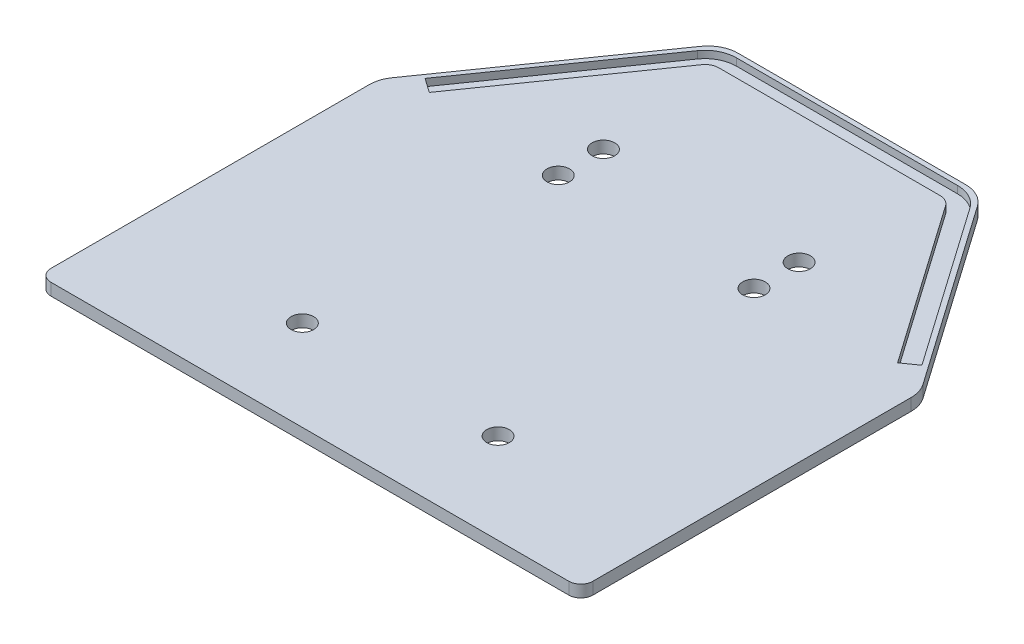
SolidWorks part; units mm, degrees
note: The reader was unsure of these and kept them because the rebuilt part matched: shared geometry of "Sketch5<5>".
ref_plane "Front Plane" through (0, 0, 0) normal (0, 0, 1) x (1, 0, 0)
ref_plane "Top Plane" through (0, 0, 0) normal (0, 1, 0) x (1, 0, 0)
ref_plane "Right Plane" through (0, 0, 0) normal (1, 0, 0) x (0, 0, -1)
sketch "TruckMountingHoles" plane through (0, 0, 0) normal (0, 1, 0) x (1, 0, 0)
  line L0 (-20.6375, 22.225) -> (20.6375, 22.225) construction
  line L1 (-20.6375, -31.75) -> (20.6375, -31.75)
  line L2 (-20.6375, -31.75) -> (-20.6375, 31.75)
  line L3 (-20.6375, 31.75) -> (20.6375, 31.75)
  line L4 (20.6375, -31.75) -> (20.6375, 31.75)
  line L5 (-20.6375, -31.75) -> (20.6375, 31.75) construction
  line L6 (-20.6375, 31.75) -> (20.6375, -31.75) construction
  circle A0 centre (-20.6375, 22.225) radius 2.3813
  circle A1 centre (-20.6375, 31.75) radius 2.3813
  circle A2 centre (20.6375, 31.75) radius 2.3813
  circle A3 centre (20.6375, 22.225) radius 2.3813
  circle A4 centre (20.6375, -31.75) radius 2.3813
  circle A5 centre (-20.6375, -31.75) radius 2.3813
  point P0 (0, 0)
  dimension "D3" = 4.7625
  dimension "D1" = 41.275
  dimension "D2" = 63.5
  dimension "D4" = 53.975
sketch "Sketch2" plane through (0, 0, 0) normal (0, 1, 0) x (1, 0, 0)
  line L1 (-57.15, -50.8) -> (57.15, -50.8)
  line L2 (-57.15, -50.8) -> (-57.15, 50.8)
  line L3 (-57.15, 50.8) -> (57.15, 50.8)
  line L4 (57.15, -50.8) -> (57.15, 50.8)
  line L5 (-57.15, -50.8) -> (57.15, 50.8) construction
  line L6 (-57.15, 50.8) -> (57.15, -50.8) construction
  point P0 (0, 0)
  dimension "D1" = 114.3
  dimension "D2" = 101.6
extrude "Boss-Extrude1" add sketch "Sketch2" along normal blind 2.54
sketch "Sketch3" plane through (0, 2.54, 0) normal (0, 1, 0) x (1, 0, 0)
  line L4 (57.15, 50.8) -> (-57.15, 50.8) construction
  line L5 (-30.1625, -50.8) -> (-11.1125, -50.8)
  line L6 (-30.1625, -50.8) -> (-30.1625, 50.8)
  line L7 (-30.1625, 50.8) -> (-11.1125, 50.8)
  line L13 (-11.1125, -50.8) -> (-11.1125, 50.8)
  line L14 (-30.1625, -50.8) -> (-11.1125, 50.8) construction
  line L15 (-30.1625, 50.8) -> (-11.1125, -50.8) construction
  line L17 (-20.6375, -31.75) -> (-20.6375, 31.75) construction
  line L18 (0, 50.8) -> (0, -50.8) construction
  line L19 (-57.15, -50.8) -> (57.15, -50.8) construction
  line L20 (30.1625, 50.8) -> (11.1125, -50.8) construction
  line L21 (30.1625, -50.8) -> (11.1125, 50.8) construction
  line L22 (11.1125, -50.8) -> (11.1125, 50.8)
  line L23 (30.1625, 50.8) -> (11.1125, 50.8)
  line L24 (30.1625, -50.8) -> (30.1625, 50.8)
  line L25 (30.1625, -50.8) -> (11.1125, -50.8)
  line L26 (-57.15, -50.8) -> (57.15, -50.8)
  line L27 (-30.1625, -12.7) -> (30.1625, -12.7)
  line L28 (-30.1625, -12.7) -> (-30.1625, 12.7)
  line L29 (-30.1625, 12.7) -> (30.1625, 12.7)
  line L30 (30.1625, -12.7) -> (30.1625, 12.7)
  line L31 (-30.1625, -12.7) -> (30.1625, 12.7) construction
  line L32 (-30.1625, 12.7) -> (30.1625, -12.7) construction
  line L33 (-30.1625, 41.7056) -> (-23.7946, 50.8)
  line L35 (-36.2596, 37.4265) -> (-44.9423, 25.0262)
  line L36 (30.1625, 41.7056) -> (23.7946, 50.8)
  point P0 (-20.6375, 0)
  point P17 (20.6375, 0)
  point P18 (0, 0)
  dimension "D1" = 19.05
  dimension "D2" = 25.4
  dimension "D3" = 2.54
extrude "Boss-Extrude2" add sketch "Sketch3" along normal blind 2.54
extrude "Cut-Extrude1" cut sketch "TruckMountingHoles" along normal through all contours A1 | A0 | A4 | A5 | A3 | A2
fillet "Fillet1" radius 2.54 4 edges at (57.15, 1.27, -50.8) (57.15, 1.27, 50.8) (-57.15, 1.27, -50.8) (-57.15, 1.27, 50.8)
sketch "Sketch5" plane through (0, 2.54, 0) normal (0, 1, 0) x (1, 0, 0)
  line L1 (57.15, -48.26) -> (57.15, 48.26) construction
  line L2 (0, 50.8) -> (0, 0) construction
  line L3 (27.305, 63.5) -> (-27.305, 63.5)
  line L4 (23.7946, 50.8) -> (-25.5007, 50.8)
  line L5 (57.15, 20.8769) -> (27.305, 63.5)
  line L6 (-57.15, 20.8769) -> (-27.305, 63.5)
  line L17 (57.15, -48.26) -> (57.15, 48.26)
  line L19 (30.1625, 41.7056) -> (30.1625, 12.7)
  line L20 (30.1625, 12.7) -> (11.1125, 12.7)
  line L21 (11.1125, 12.7) -> (11.1125, 50.8)
  line L22 (11.1125, 50.8) -> (-11.1125, 50.8)
  line L23 (-11.1125, 50.8) -> (-11.1125, 12.7)
  line L24 (-11.1125, 12.7) -> (-30.1625, 12.7)
  line L25 (-30.1625, 12.7) -> (-30.1625, 41.7056)
  line L26 (-23.7946, 50.8) -> (-54.61, 50.8)
  line L27 (-57.15, 48.26) -> (-57.15, -48.26)
  line L28 (-54.61, -50.8) -> (-30.1625, -50.8)
  line L29 (-30.1625, -50.8) -> (-30.1625, -12.7)
  line L30 (-30.1625, -12.7) -> (-11.1125, -12.7)
  line L31 (57.15, -48.26) -> (57.15, 48.26)
  line L51 (30.1625, 41.7056) -> (30.1625, 12.7)
  line L52 (30.1625, 12.7) -> (11.1125, 12.7)
  line L53 (11.1125, 12.7) -> (11.1125, 50.8)
  line L54 (11.1125, 50.8) -> (-11.1125, 50.8)
  line L55 (-11.1125, 50.8) -> (-11.1125, 12.7)
  line L56 (-11.1125, 12.7) -> (-30.1625, 12.7)
  line L57 (-30.1625, 12.7) -> (-30.1625, 41.7056)
  line L58 (-23.7946, 50.8) -> (-54.61, 50.8)
  line L59 (-57.15, 48.26) -> (-57.15, -48.26)
  line L60 (-54.61, -50.8) -> (-30.1625, -50.8)
  line L61 (-30.1625, -50.8) -> (-30.1625, -12.7)
  line L62 (-30.1625, -12.7) -> (-11.1125, -12.7)
  line L71 (54.61, 50.8) -> (23.7946, 50.8)
  line L72 (-30.1625, 41.7056) -> (-23.7946, 50.8)
  line L73 (-30.1625, 41.7056) -> (-23.7946, 50.8)
  line L82 (54.61, 50.8) -> (23.7946, 50.8)
  line L84 (30.1625, -12.7) -> (30.1625, -50.8)
  line L86 (11.1125, -12.7) -> (30.1625, -12.7)
  line L87 (11.1125, -12.7) -> (30.1625, -12.7)
  line L88 (30.1625, -12.7) -> (30.1625, -50.8)
  line L89 (30.1625, -50.8) -> (54.61, -50.8)
  line L90 (30.1625, -50.8) -> (54.61, -50.8)
  line L91 (23.7946, 50.8) -> (30.1625, 41.7056)
  line L92 (23.7946, 50.8) -> (30.1625, 41.7056)
  line L93 (-11.1125, -12.7) -> (-11.1125, -50.8)
  line L94 (-11.1125, -12.7) -> (-11.1125, -50.8)
  line L95 (-11.1125, -50.8) -> (11.1125, -50.8)
  line L96 (-11.1125, -50.8) -> (11.1125, -50.8)
  line L97 (11.1125, -50.8) -> (11.1125, -12.7)
  line L98 (11.1125, -50.8) -> (11.1125, -12.7)
  arc A7 (57.15, 48.26) -> (54.61, 50.8) centre (54.61, 48.26) ccw
  arc A8 (-54.61, 50.8) -> (-57.15, 48.26) centre (-54.61, 48.26) ccw
  arc A13 (-57.15, -48.26) -> (-54.61, -50.8) centre (-54.61, -48.26) ccw
  arc A14 (57.15, 48.26) -> (54.61, 50.8) centre (54.61, 48.26) ccw
  arc A16 (-54.61, 50.8) -> (-57.15, 48.26) centre (-54.61, 48.26) ccw
  arc A17 (-57.15, -48.26) -> (-54.61, -50.8) centre (-54.61, -48.26) ccw
  arc A18 (54.61, -50.8) -> (57.15, -48.26) centre (54.61, -48.26) ccw
  arc A19 (54.61, -50.8) -> (57.15, -48.26) centre (54.61, -48.26) ccw
  dimension "D1" = 0
  dimension "D2" = 12.7
  dimension "D3" = 54.61
extrude "Cut-Extrude3" cut sketch "Sketch5" against normal through all and the other way through all
extrude "Boss-Extrude3" add sketch "Sketch5<5>" against normal up to surface (2.54 mm away) up to face at (20.6375, 0, -29.3687)
sketch "Sketch5<5>" plane through (0, 2.54, 0) normal (0, 1, 0) x (1, 0, 0) same geometry as "Sketch5"
sketch "Sketch6" plane through (0, 2.54, 0) normal (0, 1, 0) x (1, 0, 0)
  line L8 (25.9391, 57.7011) -> (49.4458, 24.13)
  line L9 (-23.3383, 59.055) -> (23.3383, 59.055)
  line L10 (-49.4458, 24.13) -> (-25.9391, 57.7011)
  line L11 (-52.0466, 25.9511) -> (-49.4458, 24.13)
  line L12 (-28.5399, 59.5222) -> (-52.0466, 25.9511)
  line L13 (23.3383, 62.23) -> (-23.3383, 62.23)
  line L14 (52.0466, 25.9511) -> (28.5399, 59.5222)
  line L15 (49.4458, 24.13) -> (52.0466, 25.9511)
  line L16 (25.9391, 57.7011) -> (49.4458, 24.13)
  line L17 (-23.3383, 59.055) -> (23.3383, 59.055)
  line L18 (-49.4458, 24.13) -> (-25.9391, 57.7011)
  line L19 (-52.0466, 25.9511) -> (-49.4458, 24.13)
  line L20 (-28.5399, 59.5222) -> (-52.0466, 25.9511)
  line L21 (23.3383, 62.23) -> (-23.3383, 62.23)
  line L22 (52.0466, 25.9511) -> (28.5399, 59.5222)
  line L23 (49.4458, 24.13) -> (52.0466, 25.9511)
  line L24 (49.3835, 23.7762) -> (52.4004, 25.8887)
  line L25 (25.731, 57.5554) -> (49.3835, 23.7762)
  line L26 (-23.3383, 58.801) -> (23.3383, 58.801)
  line L27 (-49.3835, 23.7762) -> (-25.731, 57.5554)
  line L28 (-52.4004, 25.8887) -> (-49.3835, 23.7762)
  line L29 (-28.748, 59.6679) -> (-52.4004, 25.8887)
  line L30 (23.3383, 62.484) -> (-23.3383, 62.484)
  line L31 (52.4004, 25.8887) -> (28.748, 59.6679)
  line L32 (49.3835, 23.7762) -> (52.4004, 25.8887)
  line L33 (25.731, 57.5554) -> (49.3835, 23.7762)
  line L34 (-23.3383, 58.801) -> (23.3383, 58.801)
  line L35 (-49.3835, 23.7762) -> (-25.731, 57.5554)
  line L36 (-52.4004, 25.8887) -> (-49.3835, 23.7762)
  line L37 (-28.748, 59.6679) -> (-52.4004, 25.8887)
  line L38 (23.3383, 62.484) -> (-23.3383, 62.484)
  line L39 (52.4004, 25.8887) -> (28.748, 59.6679)
  arc A4 (25.9391, 57.7011) -> (23.3383, 59.055) centre (23.3383, 55.88) ccw
  arc A5 (-23.3383, 59.055) -> (-25.9391, 57.7011) centre (-23.3383, 55.88) ccw
  arc A6 (-23.3383, 62.23) -> (-28.5399, 59.5222) centre (-23.3383, 55.88) ccw
  arc A7 (28.5399, 59.5222) -> (23.3383, 62.23) centre (23.3383, 55.88) ccw
  arc A8 (25.9391, 57.7011) -> (23.3383, 59.055) centre (23.3383, 55.88) ccw
  arc A9 (-23.3383, 59.055) -> (-25.9391, 57.7011) centre (-23.3383, 55.88) ccw
  arc A10 (-23.3383, 62.23) -> (-28.5399, 59.5222) centre (-23.3383, 55.88) ccw
  arc A11 (28.5399, 59.5222) -> (23.3383, 62.23) centre (23.3383, 55.88) ccw
  arc A12 (25.731, 57.5554) -> (23.3383, 58.801) centre (23.3383, 55.88) ccw
  arc A13 (-23.3383, 58.801) -> (-25.731, 57.5554) centre (-23.3383, 55.88) ccw
  arc A14 (-23.3383, 62.484) -> (-28.748, 59.6679) centre (-23.3383, 55.88) ccw
  arc A15 (28.748, 59.6679) -> (23.3383, 62.484) centre (23.3383, 55.88) ccw
  arc A16 (25.731, 57.5554) -> (23.3383, 58.801) centre (23.3383, 55.88) ccw
  arc A17 (-23.3383, 58.801) -> (-25.731, 57.5554) centre (-23.3383, 55.88) ccw
  arc A18 (-23.3383, 62.484) -> (-28.748, 59.6679) centre (-23.3383, 55.88) ccw
  arc A19 (28.748, 59.6679) -> (23.3383, 62.484) centre (23.3383, 55.88) ccw
  dimension "D1" = 0
  dimension "D2" = 0
extrude "Cut-Extrude4" cut sketch "Sketch6" against normal offset from surface (1.526 mm away) 0.254 contours A19 L38 A18 L37 L36 L35 A17 L34 A16 L33 L32 L39
fillet "Fillet2" radius 6.35 4 edges at (-57.15, 1.27, -20.8769) (-27.305, 1.27, -63.5) (27.305, 1.27, -63.5) (57.15, 1.27, -20.8769)
sketch "Sketch7" plane through (0, 0, 0) normal (0, -1, 0) x (1, 0, 0)
  line L1 (57.15, 48.26) -> (57.15, -18.8748) construction
  line L2 (56.0016, -22.517) -> (29.201, -60.7922) construction
  point P0 (57.15, -20.8769)
sketch "Sketch8" plane through (0, 2.54, 0) normal (0, 1, 0) x (1, 0, 0)
  line L0 (-11.1125, -48.26) -> (11.1125, -48.26)
  line L14 (-29.201, 60.7922) -> (-56.0016, 22.517)
  line L15 (-57.15, 18.8748) -> (-57.15, -48.26)
  line L16 (-54.61, -50.8) -> (-30.1625, -50.8)
  line L17 (-30.1625, -50.8) -> (-30.1625, -12.7)
  line L18 (-30.1625, -12.7) -> (-11.1125, -12.7)
  line L19 (-11.1125, -12.7) -> (-11.1125, -50.8)
  line L20 (-11.1125, -50.8) -> (11.1125, -50.8)
  line L21 (11.1125, -50.8) -> (11.1125, -12.7)
  line L22 (11.1125, -12.7) -> (30.1625, -12.7)
  line L23 (30.1625, -12.7) -> (30.1625, -50.8)
  line L24 (30.1625, -50.8) -> (54.61, -50.8)
  line L25 (57.15, -48.26) -> (57.15, 18.8748)
  line L26 (56.0016, 22.517) -> (29.201, 60.7922)
  line L27 (23.9994, 63.5) -> (-23.9994, 63.5)
  line L28 (-29.201, 60.7922) -> (-56.0016, 22.517)
  line L29 (-57.15, 18.8748) -> (-57.15, -48.26)
  line L30 (-54.61, -50.8) -> (-30.1625, -50.8)
  line L31 (-30.1625, -50.8) -> (-30.1625, -12.7)
  line L32 (-30.1625, -12.7) -> (-11.1125, -12.7)
  line L33 (-11.1125, -12.7) -> (-11.1125, -50.8)
  line L34 (-11.1125, -50.8) -> (11.1125, -50.8)
  line L35 (11.1125, -50.8) -> (11.1125, -12.7)
  line L36 (11.1125, -12.7) -> (30.1625, -12.7)
  line L37 (30.1625, -12.7) -> (30.1625, -50.8)
  line L38 (30.1625, -50.8) -> (54.61, -50.8)
  line L39 (57.15, -48.26) -> (57.15, 18.8748)
  line L40 (56.0016, 22.517) -> (29.201, 60.7922)
  line L41 (23.9994, 63.5) -> (-23.9994, 63.5)
  arc A6 (-56.0016, 22.517) -> (-57.15, 18.8748) centre (-50.8, 18.8748) ccw
  arc A7 (-57.15, -48.26) -> (-54.61, -50.8) centre (-54.61, -48.26) ccw
  arc A8 (54.61, -50.8) -> (57.15, -48.26) centre (54.61, -48.26) ccw
  arc A9 (57.15, 18.8748) -> (56.0016, 22.517) centre (50.8, 18.8748) ccw
  arc A10 (29.201, 60.7922) -> (23.9994, 63.5) centre (23.9994, 57.15) ccw
  arc A11 (-23.9994, 63.5) -> (-29.201, 60.7922) centre (-23.9994, 57.15) ccw
  arc A12 (-56.0016, 22.517) -> (-57.15, 18.8748) centre (-50.8, 18.8748) ccw
  arc A13 (-57.15, -48.26) -> (-54.61, -50.8) centre (-54.61, -48.26) ccw
  arc A14 (54.61, -50.8) -> (57.15, -48.26) centre (54.61, -48.26) ccw
  arc A15 (57.15, 18.8748) -> (56.0016, 22.517) centre (50.8, 18.8748) ccw
  arc A16 (29.201, 60.7922) -> (23.9994, 63.5) centre (23.9994, 57.15) ccw
  arc A17 (-23.9994, 63.5) -> (-29.201, 60.7922) centre (-23.9994, 57.15) ccw
  line M51 (-11.1125, -12.7) -> (-11.1125, -50.8)
  line M52 (-11.1125, -50.8) -> (11.1125, -50.8)
  line M53 (11.1125, -50.8) -> (11.1125, -12.7)
  dimension "D2" = 2.54
  dimension "D1" = 0
extrude "Boss-Extrude4" add sketch "Sketch8" along normal up to surface (2.54 mm away) contours L0 M51 M52 M53 up to face at (-20.6375, 5.08, 34.1313)
sketch "Sketch9" plane through (0, 0, 50.8) normal (0, 0, 1) x (1, 0, 0)
  line L0 (11.1125, 9.398) -> (5.08, 9.398) construction
  line L1 (11.1125, 9.398) -> (5.08, 9.398)
  line L4 (-6.35, 8.128) -> (-6.35, 5.18)
  line L5 (-5.08, 3.91) -> (5.08, 3.91)
  line L6 (6.35, 5.18) -> (6.35, 8.128)
  line L7 (5.08, 9.398) -> (-5.08, 9.398)
  line L8 (-6.35, 8.128) -> (-6.35, 5.18)
  line L9 (-5.08, 3.91) -> (5.08, 3.91)
  line L10 (6.35, 5.18) -> (6.35, 8.128)
  line L11 (5.08, 9.398) -> (-5.08, 9.398)
  arc A4 (-6.35, 5.18) -> (-5.08, 3.91) centre (-5.08, 5.18) ccw
  arc A5 (5.08, 3.91) -> (6.35, 5.18) centre (5.08, 5.18) ccw
  arc A6 (6.35, 8.128) -> (5.08, 9.398) centre (5.08, 8.128) ccw
  arc A7 (-5.08, 9.398) -> (-6.35, 8.128) centre (-5.08, 8.128) ccw
  arc A8 (-6.35, 5.18) -> (-5.08, 3.91) centre (-5.08, 5.18) ccw
  arc A9 (5.08, 3.91) -> (6.35, 5.18) centre (5.08, 5.18) ccw
  arc A10 (6.35, 8.128) -> (5.08, 9.398) centre (5.08, 8.128) ccw
  arc A11 (-5.08, 9.398) -> (-6.35, 8.128) centre (-5.08, 8.128) ccw
  line M13 (30.1625, 5.08) -> (-30.1625, 5.08)
  dimension "D1" = 0
extrude "Cut-Extrude5" cut sketch "Sketch9" against normal blind 2.54 contours L9 A9 A8 M13
sketch "Sketch10" plane through (0, 5.08, 0) normal (0, 1, 0) x (1, 0, 0)
  line L0 (0, 50.8) -> (30.1625, 50.8) construction
  line L1 (-30.1625, -50.8) -> (30.1625, -50.8)
  line L2 (-30.1625, -50.8) -> (-30.1625, 50.8)
  line L3 (-30.1625, 50.8) -> (30.1625, 50.8)
  line L4 (30.1625, -50.8) -> (30.1625, 50.8)
  line L5 (30.1625, -50.8) -> (30.1625, -12.7) construction
extrude "Cut-Extrude6" cut sketch "Sketch10" against normal up to surface (2.54 mm away) up to face at (0, 2.54, -48.188)
